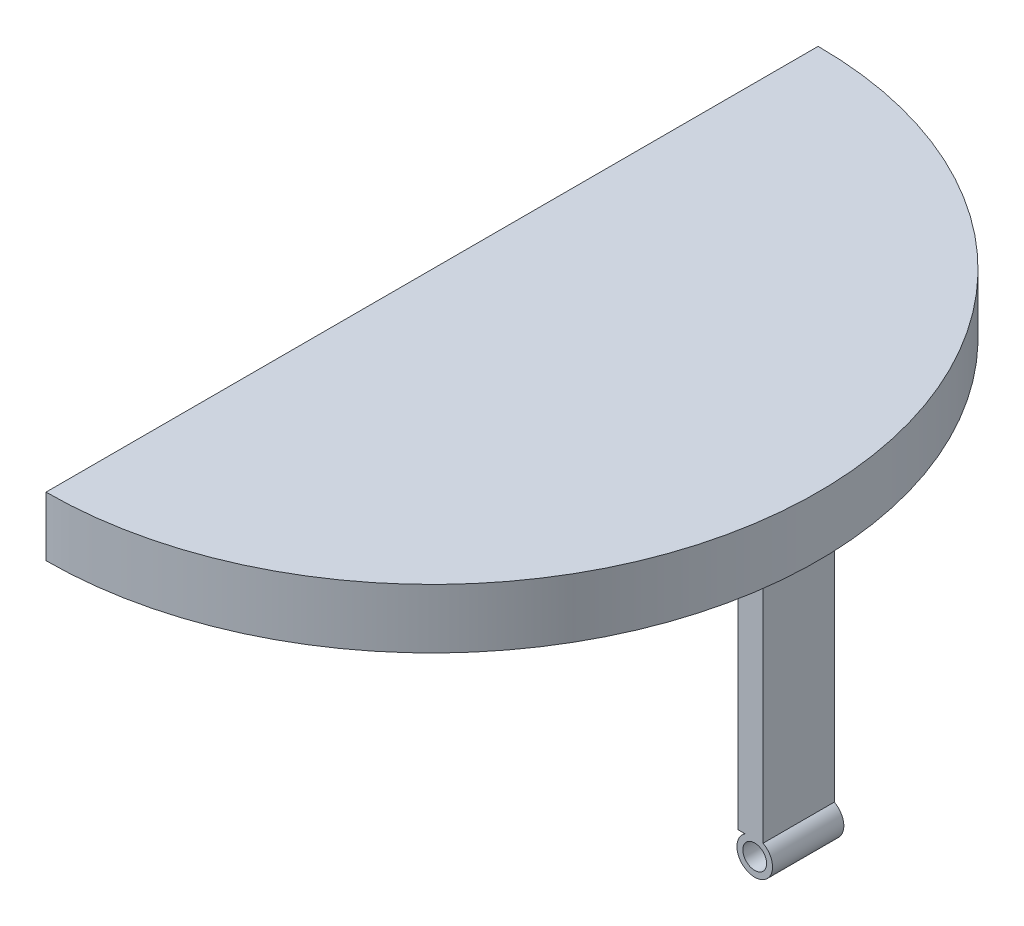
SolidWorks part; units mm, degrees
ref_plane "Ebene vorne" through (0, 0, 0) normal (0, 0, 1) x (1, 0, 0)
ref_plane "Ebene oben" through (0, 0, 0) normal (0, 1, 0) x (1, 0, 0)
ref_plane "Ebene rechts" through (0, 0, 0) normal (1, 0, 0) x (0, 0, -1)
sketch "Skizze1" plane through (0, 0, 0) normal (0, 1, 0) x (1, 0, 0)
  line L0 (0, 0) -> (0, -65)
  arc A0 (0, -65) -> (0, 0) centre (0, -32.5) ccw
  dimension "D1" = 65
extrude "Aufsatz-Linear austragen1" add sketch "Skizze1" along normal blind 5
sketch "Skizze3" plane through (0, 0, 0) normal (0, -1, 0) x (1, 0, 0)
  line L0 (30.8409, 35.4822) -> (30.8409, 29.4822)
  line L2 (30.8409, 29.4822) -> (28.7231, 29.4822)
  line L3 (28.7231, 29.4822) -> (28.7231, 35.4822)
  line L4 (28.7231, 35.4822) -> (30.8409, 35.4822)
  line L5 (32.5, 32.5) -> (29.7856, 32.5) construction
  arc A2 (0, 0) -> (0, 65) centre (0, 32.5) ccw construction
extrude "Aufsatz-Linear austragen2" add sketch "Skizze3" along normal blind 20
sketch "Skizze5" plane through (0, 0.6923, 29.4822) normal (0, 0, -1) x (-1, 0, 0)
  circle A0 centre (-30.1437, -21.9579) radius 1.5
extrude "Aufsatz-Linear austragen4" add sketch "Skizze5" against normal blind 6
sketch "Skizze7" plane through (0, 0, 29.4822) normal (0, 0, -1) x (-1, 0, 0)
  circle A0 centre (-30.1438, -21.2655) radius 1
  point P2 (-30.0831, -22.796)
  point P3 (-30.0521, -22.8063)
  point P4 (-30.1391, -21.2735)
  dimension "D1" = 1.5
extrude "Schnitt-Linear austragen2" cut sketch "Skizze7" against normal blind 6
